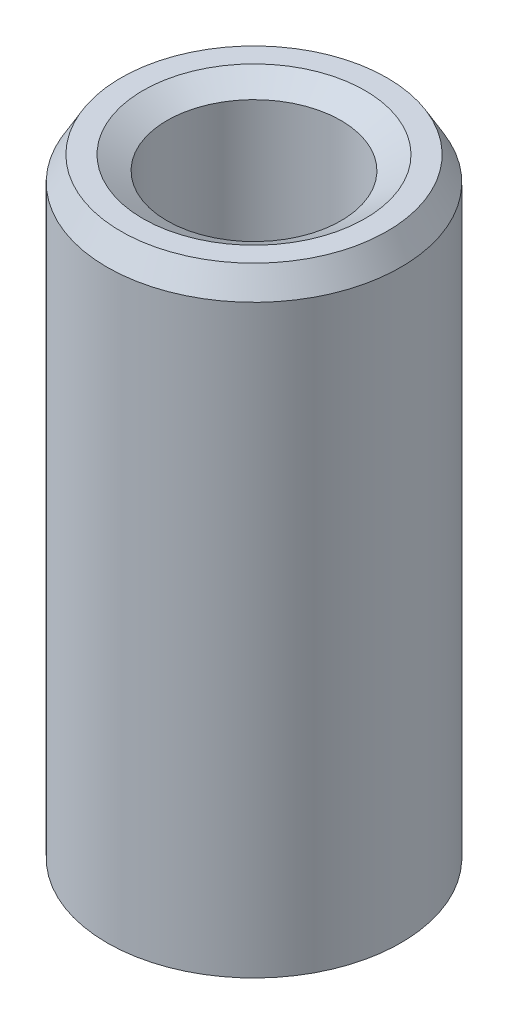
SolidWorks part; units mm, degrees
ref_plane "Front Plane" through (0, 0, 0) normal (0, 0, 1) x (1, 0, 0)
ref_plane "Top Plane" through (0, 0, 0) normal (0, 1, 0) x (1, 0, 0)
ref_plane "Right Plane" through (0, 0, 0) normal (1, 0, 0) x (0, 0, -1)
sketch "Sketch1" plane through (0, 0, 0) normal (0, 1, 0) x (1, 0, 0)
  circle A0 centre (0, 0) radius 17.5
  dimension "SLEEVE_OD" = 35
extrude "Boss-Extrude1" add sketch "Sketch1" along normal blind 74.2112
sketch "Sketch2" plane through (0, 0, 0) normal (0, 1, 0) x (1, 0, 0)
  circle A0 centre (0, 0) radius 10.356
  dimension "BORE_D" = 20.712
extrude "Cut-Extrude1" cut sketch "Sketch2" along normal through all
chamfer "Chamfer1" distance 2.868 angle 30 4 edges at (0, 74.2112, 10.356) (0, 0, 10.356) (0, 0, 17.5) (0, 74.2112, 17.5) first distance on face at (0, 74.2112, 10.356) first distance on face at (0, 0, 10.356) first distance on face at (0, 74.2112, 17.5)
